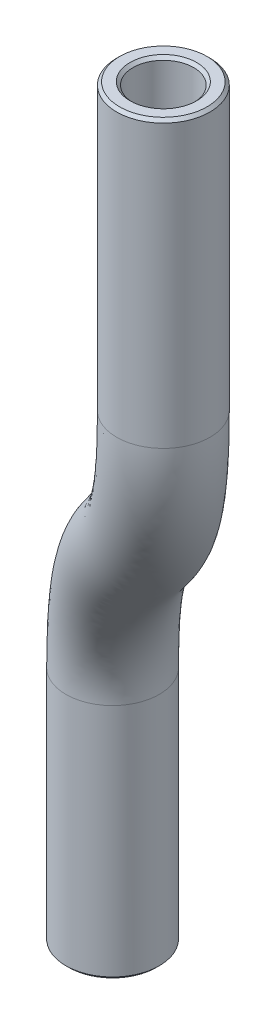
SolidWorks part; units mm, degrees
ref_plane "Front Plane" through (0, 0, 0) normal (0, 0, 1) x (1, 0, 0)
ref_plane "Top Plane" through (0, 0, 0) normal (0, 1, 0) x (1, 0, 0)
ref_plane "Right Plane" through (0, 0, 0) normal (1, 0, 0) x (0, 0, -1)
sketch3d "3DSketch1"
  line L0 (93.825, -93.2823, 17.525) -> (93.825, -103.4823, 17.525)
  line L1 (104.325, -74.325, 25.85) -> (104.325, -62.125, 25.85)
  spline S0 degree 3 poles (93.825, -93.2823, 17.525) (93.825, -89.4579, 17.525) (99.075, -83.8401, 21.6875) (104.325, -78.2562, 25.85) (104.325, -74.325, 25.85) knots 0 0 0 0 0.494206 1 1 1 1
sketch "Sketch3" plane through (0, -95.3823, 0) normal (0, 1, 0) x (1, 0, 0)
  circle A0 centre (93.825, -17.525) radius 2
  circle A1 centre (93.825, -17.525) radius 1.3
  circle A4 centre (93.825, -17.525) radius 3.5 construction
  dimension "D1" = 2.6
  dimension "D2" = 4
sweep "Sweep1" add profiles "Sketch3" path "3DSketch1"
chamfer "Chamfer1" distance 0.127 angle 45 4 edges at (91.825, -103.4823, 17.525) (92.525, -103.4823, 17.525) (102.325, -62.125, 25.85) (103.025, -62.125, 25.85)
